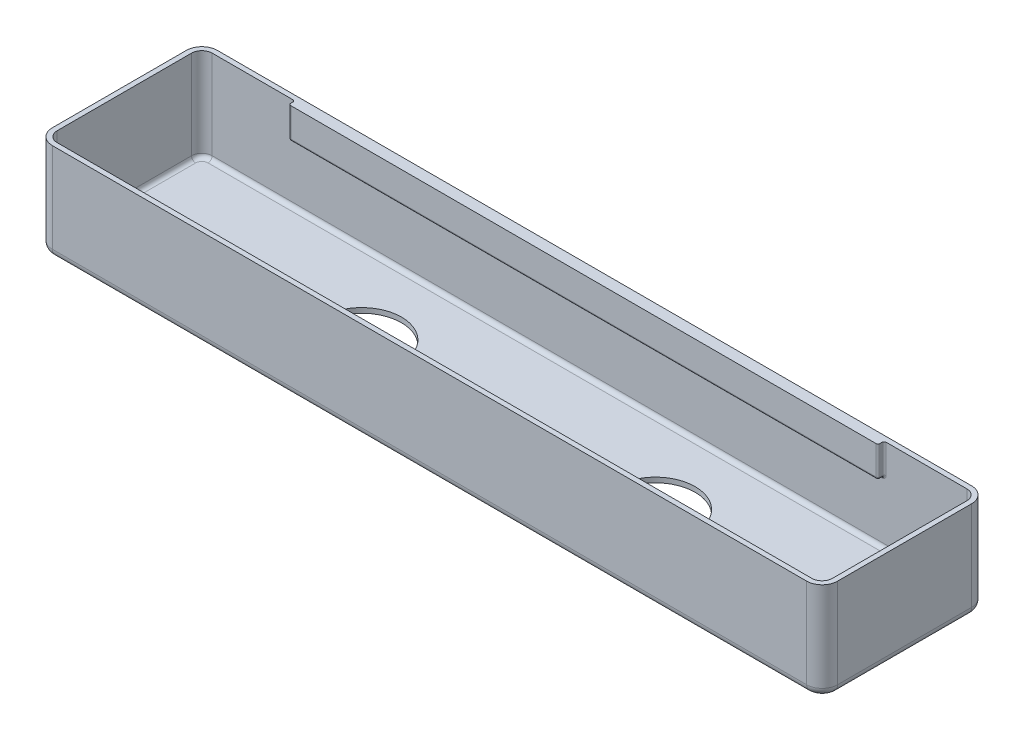
SolidWorks part; units mm, degrees
material "NEOPRENE"
ref_plane "Front" through (0, 0, 0) normal (0, 0, 1) x (1, 0, 0)
ref_plane "Top" through (0, 0, 0) normal (0, 1, 0) x (1, 0, 0)
ref_plane "Right" through (0, 0, 0) normal (1, 0, 0) x (0, 0, -1)
sketch "Sketch1" plane through (0, 0, 0) normal (0, 1, 0) x (1, 0, 0)
  line L0 (-119.0625, 0) -> (-120.5865, 0) construction
  line L1 (-120.5865, 25.3365) -> (120.5865, 25.3365)
  line L2 (-120.5865, 25.3365) -> (-120.5865, -25.3365)
  line L3 (-120.5865, -25.3365) -> (120.5865, -25.3365)
  line L4 (120.5865, 25.3365) -> (120.5865, -25.3365)
  line L5 (-120.5865, 25.3365) -> (120.5865, -25.3365) construction
  line L6 (-120.5865, -25.3365) -> (120.5865, 25.3365) construction
  line L7 (119.0625, 23.8125) -> (-119.0625, 23.8125)
  line L8 (119.0625, 23.8125) -> (119.0625, -23.8125)
  line L9 (119.0625, -23.8125) -> (-119.0625, -23.8125)
  line L10 (-119.0625, 23.8125) -> (-119.0625, -23.8125)
  line L11 (119.0625, 23.8125) -> (-119.0625, -23.8125) construction
  line L12 (119.0625, -23.8125) -> (-119.0625, 23.8125) construction
  line L13 (0, 23.8125) -> (0, 25.3365) construction
  point P0 (0, 0)
  point P6 (0, 0)
  dimension "D1" = 238.125
  dimension "D2" = 47.625
  dimension "THICKNESS" = 1.524
extrude "Boss-Extrude1" add sketch "Sketch1" along normal blind 38.1
sketch "Sketch2" plane through (0, 0, 0) normal (0, -1, 0) x (1, 0, 0)
  line L4 (120.5865, -25.3365) -> (120.5865, 25.3365)
  line L5 (120.5865, 25.3365) -> (-120.5865, 25.3365)
  line L6 (-120.5865, 25.3365) -> (-120.5865, -25.3365)
  line L7 (-120.5865, -25.3365) -> (120.5865, -25.3365)
  line L8 (120.5865, -25.3365) -> (120.5865, 25.3365)
  line L9 (120.5865, 25.3365) -> (-120.5865, 25.3365)
  line L10 (-120.5865, 25.3365) -> (-120.5865, -25.3365)
  line L11 (-120.5865, -25.3365) -> (120.5865, -25.3365)
  arc A0 (104.3365, 1.0115) -> (104.3365, 5.2115) centre (104.3365, 3.1115) ccw construction
  arc A1 (104.3365, 5.2115) -> (104.3365, 1.0115) centre (104.3365, 3.1115) ccw construction
  arc A2 (73.3365, 1.0115) -> (73.3365, 5.2115) centre (73.3365, 3.1115) ccw construction
  arc A3 (73.3365, 5.2115) -> (73.3365, 1.0115) centre (73.3365, 3.1115) ccw construction
  arc A4 (104.3365, 1.0115) -> (104.3365, 5.2115) centre (104.3365, 3.1115) ccw
  arc A5 (104.3365, 5.2115) -> (104.3365, 1.0115) centre (104.3365, 3.1115) ccw
  arc A6 (73.3365, 1.0115) -> (73.3365, 5.2115) centre (73.3365, 3.1115) ccw
  arc A7 (73.3365, 5.2115) -> (73.3365, 1.0115) centre (73.3365, 3.1115) ccw
  dimension "D1" = 0
extrude "Boss-Extrude2" add sketch "Sketch2" along normal blind 1.524
fillet "Fillet1" radius 3.175 4 edges at (119.0625, 19.05, -23.8125) (119.0625, 19.05, 23.8125) (-119.0625, 19.05, 23.8125) (-119.0625, 19.05, -23.8125)
fillet "Fillet2" radius 4.7625 4 edges at (-120.5865, 18.288, -25.3365) (120.5865, 18.288, -25.3365) (120.5865, 18.288, 25.3365) (-120.5865, 18.288, 25.3365)
sketch "Sketch4" plane through (0, -1.524, 0) normal (0, -1, 0) x (1, 0, 0)
  line L2 (120.5865, -20.574) -> (120.5865, 20.574) construction
  line L3 (115.824, 25.3365) -> (-115.824, 25.3365) construction
  circle A0 centre (88.8365, 3.1115) radius 12.065
  dimension "D1" = 24.13
  dimension "D3" = 22.225
  dimension "D2" = 31.75
extrude "Cut-Extrude2" [suppressed] cut sketch "Sketch4" against normal through all
sketch "Sketch5" plane through (0, 0, -23.8125) normal (0, 0, 1) x (1, 0, 0)
  line L0 (0, 0) -> (0, 28.575) construction
  line L1 (115.8875, 38.1) -> (-115.8875, 38.1) construction
  line L2 (-90.4875, 19.05) -> (90.4875, 19.05)
  line L3 (-90.4875, 19.05) -> (-90.4875, 38.1)
  line L4 (-90.4875, 38.1) -> (90.4875, 38.1)
  line L5 (90.4875, 19.05) -> (90.4875, 38.1)
  line L6 (-90.4875, 19.05) -> (90.4875, 38.1) construction
  line L7 (-90.4875, 38.1) -> (90.4875, 19.05) construction
  dimension "D1" = 180.975
  dimension "D2" = 19.05
extrude "Boss-Extrude3" add sketch "Sketch5" along normal blind 1.905
fillet "Fillet3" radius 0.635 8 edges at (0, 19.05, -21.9075) (0, 19.05, -23.8125) (-90.4875, 28.575, -23.8125) (-90.4875, 28.575, -21.9075) (90.4875, 28.575, -21.9075) (90.4875, 28.575, -23.8125) (-90.4875, 19.05, -22.86) (90.4875, 19.05, -22.86)
fillet "Fillet4" radius 1.27 8 edges at (118.1326, 0, -22.8826) (119.0625, 0, 0) (118.1326, 0, 22.8826) (0, 0, 23.8125) (-118.1326, 0, 22.8826) (-119.0625, 0, 0) (-118.1326, 0, -22.8826) (0, 0, -23.8125)
fillet "Fillet5" radius 2.54 8 edges at (-119.1916, -1.524, 23.9416) (0, -1.524, 25.3365) (119.1916, -1.524, 23.9416) (120.5865, -1.524, 0) (119.1916, -1.524, -23.9416) (0, -1.524, -25.3365) (-119.1916, -1.524, -23.9416) (-120.5865, -1.524, 0)
sketch "Sketch6" plane through (0, -1.524, 0) normal (0, -1, 0) x (1, 0, 0)
  circle A0 centre (73.3365, 3.1115) radius 2.1 construction
  circle A1 centre (73.3365, 3.1115) radius 2.1
  circle A2 centre (104.3365, 3.1115) radius 2.1 construction
  circle A3 centre (104.3365, 3.1115) radius 2.1
extrude "Boss-Extrude4" add sketch "Sketch6" against normal up to surface (1.524 mm away) up to face at (0, 0, 0)
sketch "Sketch7" plane through (0, -1.524, 0) normal (0, -1, 0) x (1, 0, 0)
  circle A0 centre (-45.2, 0.936) radius 12.192
  circle A1 centre (45, 0.936) radius 12.192
  dimension "D1" = 24.384
extrude "Cut-Extrude3" cut sketch "Sketch7" against normal through all
sketch "Sketch8" plane through (0, 38.1, 0) normal (0, 1, 0) x (1, 0, 0)
  line L0 (-90.4875, 22.5425) -> (-90.4875, 23.1775) construction
  line L1 (89.8525, 21.9075) -> (-89.8525, 21.9075) construction
  line L2 (90.4875, 22.5425) -> (90.4875, 23.1775) construction
  line L3 (115.8875, 23.8125) -> (91.1225, 23.8125) construction
  line L4 (115.824, 25.3365) -> (-115.824, 25.3365)
  line L5 (-120.5865, 20.574) -> (-120.5865, -20.574)
  line L6 (-115.824, -25.3365) -> (115.824, -25.3365)
  line L7 (120.5865, -20.574) -> (120.5865, 20.574)
  line L8 (115.824, 25.3365) -> (-115.824, 25.3365)
  line L9 (-120.5865, 20.574) -> (-120.5865, -20.574)
  line L10 (-115.824, -25.3365) -> (115.824, -25.3365)
  line L11 (120.5865, -20.574) -> (120.5865, 20.574)
  line L12 (119.0625, -20.6375) -> (119.0625, 20.6375) construction
  line L13 (-115.8875, -23.8125) -> (115.8875, -23.8125) construction
  line L14 (-91.1225, 23.8125) -> (-115.8875, 23.8125) construction
  line L15 (-119.0625, 20.6375) -> (-119.0625, -20.6375) construction
  line L16 (-90.4875, 22.5425) -> (-90.4875, 23.1775)
  line L17 (89.8525, 21.9075) -> (-89.8525, 21.9075)
  line L18 (90.4875, 22.5425) -> (90.4875, 23.1775)
  line L19 (115.8875, 23.8125) -> (91.1225, 23.8125)
  line L20 (119.0625, -20.6375) -> (119.0625, 20.6375)
  line L21 (-115.8875, -23.8125) -> (115.8875, -23.8125)
  line L22 (-91.1225, 23.8125) -> (-115.8875, 23.8125)
  line L23 (-119.0625, 20.6375) -> (-119.0625, -20.6375)
  arc A0 (-90.4875, 23.1775) -> (-91.1225, 23.8125) centre (-91.1225, 23.1775) ccw construction
  arc A1 (-90.4875, 22.5425) -> (-89.8525, 21.9075) centre (-89.8525, 22.5425) ccw construction
  arc A2 (89.8525, 21.9075) -> (90.4875, 22.5425) centre (89.8525, 22.5425) ccw construction
  arc A3 (91.1225, 23.8125) -> (90.4875, 23.1775) centre (91.1225, 23.1775) ccw construction
  arc A4 (-115.824, 25.3365) -> (-120.5865, 20.574) centre (-115.824, 20.574) ccw
  arc A5 (-120.5865, -20.574) -> (-115.824, -25.3365) centre (-115.824, -20.574) ccw
  arc A6 (115.824, -25.3365) -> (120.5865, -20.574) centre (115.824, -20.574) ccw
  arc A7 (120.5865, 20.574) -> (115.824, 25.3365) centre (115.824, 20.574) ccw
  arc A8 (-115.824, 25.3365) -> (-120.5865, 20.574) centre (-115.824, 20.574) ccw
  arc A9 (-120.5865, -20.574) -> (-115.824, -25.3365) centre (-115.824, -20.574) ccw
  arc A10 (115.824, -25.3365) -> (120.5865, -20.574) centre (115.824, -20.574) ccw
  arc A11 (120.5865, 20.574) -> (115.824, 25.3365) centre (115.824, 20.574) ccw
  arc A12 (119.0625, 20.6375) -> (115.8875, 23.8125) centre (115.8875, 20.6375) ccw construction
  arc A13 (115.8875, -23.8125) -> (119.0625, -20.6375) centre (115.8875, -20.6375) ccw construction
  arc A14 (-115.8875, 23.8125) -> (-119.0625, 20.6375) centre (-115.8875, 20.6375) ccw construction
  arc A15 (-119.0625, -20.6375) -> (-115.8875, -23.8125) centre (-115.8875, -20.6375) ccw construction
  arc A16 (-90.4875, 23.1775) -> (-91.1225, 23.8125) centre (-91.1225, 23.1775) ccw
  arc A17 (-90.4875, 22.5425) -> (-89.8525, 21.9075) centre (-89.8525, 22.5425) ccw
  arc A18 (89.8525, 21.9075) -> (90.4875, 22.5425) centre (89.8525, 22.5425) ccw
  arc A19 (91.1225, 23.8125) -> (90.4875, 23.1775) centre (91.1225, 23.1775) ccw
  arc A20 (119.0625, 20.6375) -> (115.8875, 23.8125) centre (115.8875, 20.6375) ccw
  arc A21 (115.8875, -23.8125) -> (119.0625, -20.6375) centre (115.8875, -20.6375) ccw
  arc A22 (-115.8875, 23.8125) -> (-119.0625, 20.6375) centre (-115.8875, 20.6375) ccw
  arc A23 (-119.0625, -20.6375) -> (-115.8875, -23.8125) centre (-115.8875, -20.6375) ccw
  dimension "D1" = 0
extrude "Cut-Extrude4" cut sketch "Sketch8" against normal blind 9.525
equation "\"D1@Boss-Extrude2\"=\"THICKNESS\""
